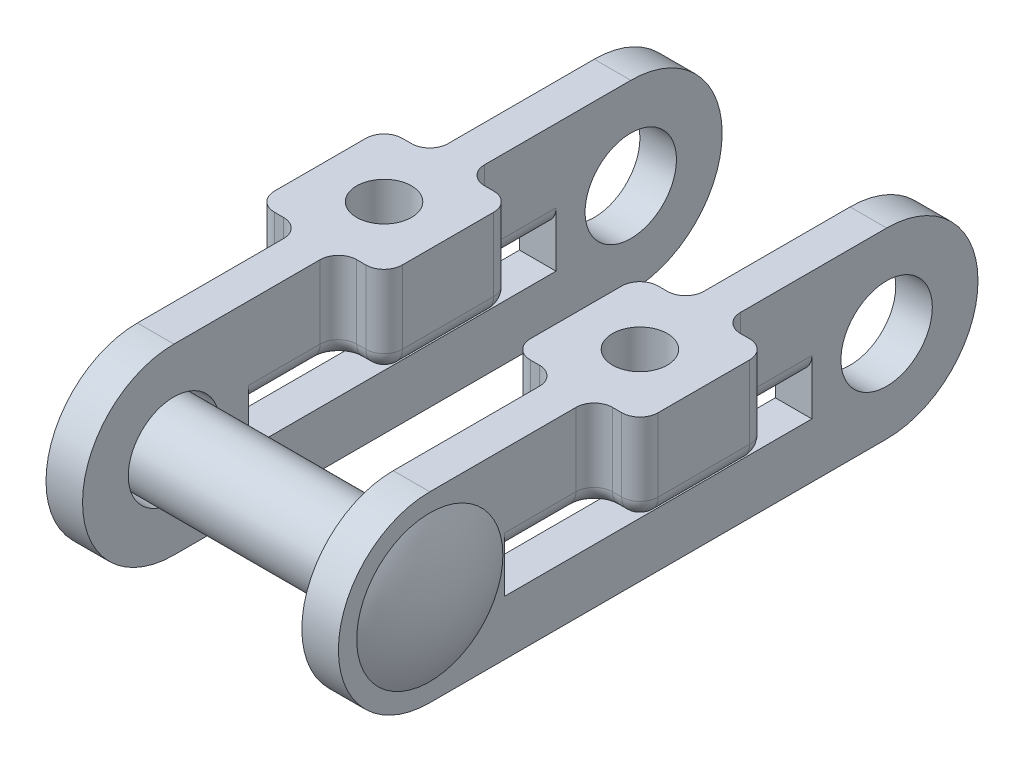
SolidWorks part; units mm, degrees
material "Alloy Steel"
ref_plane "Front Plane" through (0, 0, 0) normal (0, 0, 1) x (1, 0, 0)
ref_plane "Top Plane" through (0, 0, 0) normal (0, 1, 0) x (1, 0, 0)
ref_plane "Right Plane" through (0, 0, 0) normal (1, 0, 0) x (0, 0, -1)
sketch "Sketch1" plane through (0, 0, 0) normal (1, 0, 0) x (0, 0, -1)
  line L0 (0, 5) -> (25, 5)
  line L1 (25, -5) -> (0, -5)
  arc A0 (0, 5) -> (0, -5) centre (0, 0) ccw
  arc A1 (25, -5) -> (25, 5) centre (25, 0) ccw
  circle A2 centre (0, 0) radius 2.5
  circle A3 centre (25, 0) radius 2.5
  dimension "D1" = 25
  dimension "D2" = 10
  dimension "D3" = 5
extrude "Boss-Extrude1" add sketch "Sketch1" along normal blind 2
sketch "Sketch3" plane through (0, 5, 0) normal (0, 1, 0) x (1, 0, 0)
  line L0 (2, 0) -> (0, 0) construction
  line L1 (-2.5, 16) -> (4.5, 16)
  line L2 (-2.5, 16) -> (-2.5, 9)
  line L3 (-2.5, 9) -> (4.5, 9)
  line L4 (4.5, 16) -> (4.5, 9)
  line L5 (-2.5, 16) -> (4.5, 9) construction
  line L6 (-2.5, 9) -> (4.5, 16) construction
  line L7 (2, 25) -> (2, 0) construction
  point P0 (1, 12.5)
  point P7 (1, 0)
  point P10 (2, 12.5)
  dimension "D1" = 7
  dimension "D2" = 7
extrude "Boss-Extrude2" add sketch "Sketch3" against normal blind 5
sketch "Sketch4" plane through (0, 5, 0) normal (0, 1, 0) x (1, 0, 0)
  line L0 (4.5, 9) -> (4.5, 16) construction
  line L1 (2, 0) -> (0, 0) construction
  circle A0 centre (1, 12.5) radius 1.5
  point P4 (4.5, 12.5)
  point P7 (1, 0)
  dimension "D1" = 3
extrude "Cut-Extrude1" cut sketch "Sketch4" against normal blind 5
sketch "Sketch5" plane through (0, 0, 0) normal (0, 1, 0) x (1, 0, 0)
  line L0 (2, 25) -> (2, 16) construction
  line L1 (0, 4.0912) -> (2, 4.0912)
  line L2 (0, 4.0912) -> (0, 20.9088)
  line L3 (0, 20.9088) -> (2, 20.9088)
  line L4 (2, 4.0912) -> (2, 20.9088)
  line L5 (0, 4.0912) -> (2, 20.9088) construction
  line L6 (0, 20.9088) -> (2, 4.0912) construction
  point P0 (1, 12.5)
extrude "Cut-Extrude2" cut sketch "Sketch5" against normal blind 2
fillet "Fillet1" radius 1 8 edges at (2, 2.5, -16) (4.5, 2.5, -16) (2, 2.5, -9) (4.5, 2.5, -9) (0, 2.5, -9) (0, 2.5, -16) (-2.5, 2.5, -9) (-2.5, 2.5, -16)
fillet "Fillet2" radius 1 18 edges at (2, 0, -18.9544) (2.2929, 0, -16.2929) (3.25, 0, -16) (4.2071, 0, -15.7071) (4.5, 0, -12.5) (4.2071, 0, -9.2929) (3.25, 0, -9) (2, 0, -6.0456) (0, 0, -6.0456) (-0.2929, 0, -8.7071) (-1.25, 0, -9) (-2.2071, 0, -9.2929) (-2.5, 0, -12.5) (-2.2071, 0, -15.7071) (-1.25, 0, -16) (0, 0, -18.9544) (2.2929, 0, -8.7071) (-0.2929, 0, -16.2929)
pattern_linear "LPattern1" count 2 spacing 14 along (-1, 0, 0) of bodies 104
sketch "Sketch6" plane through (2, 0, 0) normal (1, 0, 0) x (0, 0, -1)
  circle A0 centre (0, 0) radius 2.25
  dimension "D1" = 4.5
extrude "Boss-Extrude3" add sketch "Sketch6" against normal up to surface (16 mm away) separate body up to face at (-14, 0, -27.5)
ref_plane "Plane1" through (0, 0, 0) normal (0, 1, 0) x (1, 0, 0)
sketch "Sketch7" plane through (0, 0, 0) normal (0, 1, 0) x (1, 0, 0)
  line L5 (2, -2.25) -> (2, 2.25) construction
  line L6 (-14, 2.25) -> (-14, -2.25) construction
  line L7 (2, -2.25) -> (2, 2.25) construction
  line L8 (-14, 2.25) -> (-14, -2.25) construction
  line L15 (-9.5, 12.5) -> (-2.5, 12.5) construction
  line L16 (-9.5, 10) -> (-9.5, 15) construction
  line L17 (-2.5, 15) -> (-2.5, 10) construction
  line L18 (-14, 0) -> (-14, -4)
  line L19 (-15, 0) -> (-14, 0)
  line L20 (3, 0) -> (2, 0)
  line L21 (2, 0) -> (2, -4)
  arc A3 (-15, 0) -> (-14, -4) centre (-6.5, 0) ccw
  arc A4 (3, 0) -> (2, -4) centre (-5.5, 0) cw
  dimension "D1" = 4
  dimension "D2" = 4
  dimension "D3" = 1
  dimension "D5" = 8.5
  dimension "D6" = 8.5
  dimension "D4" = 1
revolve "Revolve3" add sketch "Sketch7<4>" angle 360 about L20
sketch "Sketch7<4>" plane through (0, 0, 0) normal (0, 1, 0) x (1, 0, 0) same geometry as "Sketch7"
revolve "Revolve4" add sketch "Sketch7" angle 360 about L19
ref_plane "Plane2" through (-6, 0, 0) normal (1, 0, 0) x (0, 0, -1)
